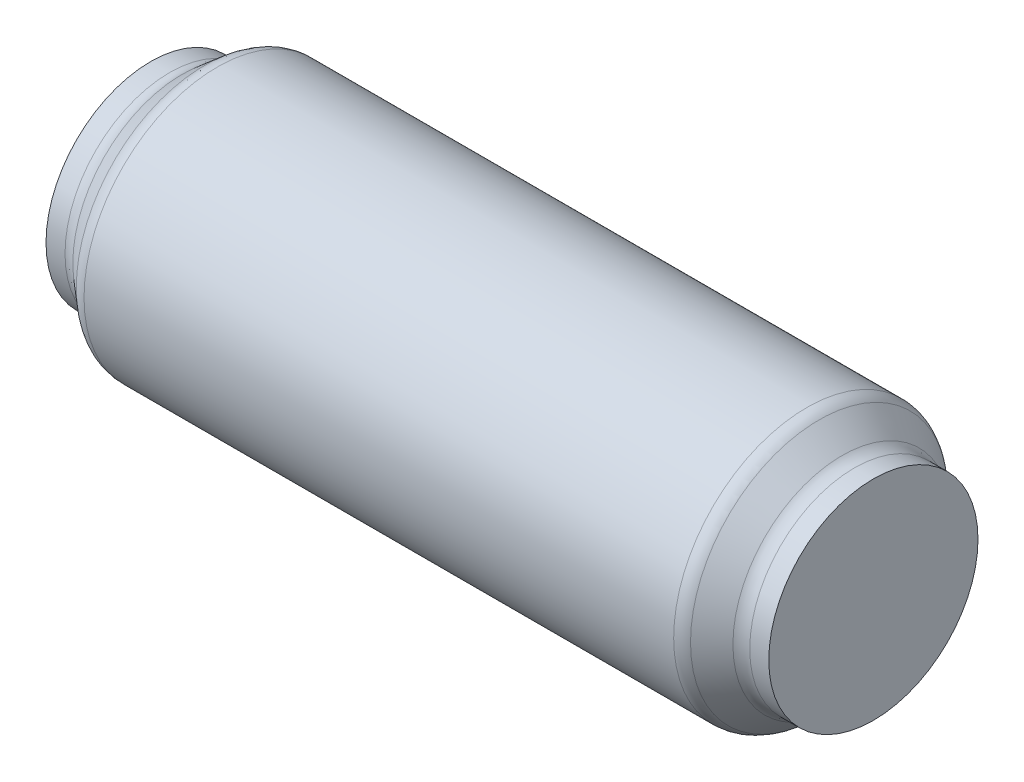
SolidWorks part; units mm, degrees
ref_plane "Front Plane" through (0, 0, 0) normal (0, 0, 1) x (1, 0, 0)
ref_plane "Top Plane" through (0, 0, 0) normal (0, 1, 0) x (1, 0, 0)
ref_plane "Right Plane" through (0, 0, 0) normal (1, 0, 0) x (0, 0, -1)
sketch "Sketch1" plane through (0, 0, 0) normal (0, 1, 0) x (1, 0, 0)
  line L0 (0, 0) -> (95, 0) construction
  line L1 (95, 0) -> (95, 27.5)
  line L2 (95, 27.5) -> (90, 27.5)
  line L3 (86.762, 28.6901) -> (80.738, 33.8099)
  line L4 (77.5, 35) -> (-77.5, 35)
  line L5 (0, 0) -> (0, 35) construction
  line L6 (-86.762, 28.6901) -> (-80.738, 33.8099)
  line L7 (-95, 27.5) -> (-90, 27.5)
  line L8 (-95, 0) -> (-95, 27.5)
  line L10 (-95, 0) -> (95, 0)
  arc A0 (90, 27.5) -> (86.762, 28.6901) centre (90, 32.5) cw
  arc A1 (80.738, 33.8099) -> (77.5, 35) centre (77.5, 30) ccw
  arc A2 (-80.738, 33.8099) -> (-77.5, 35) centre (-77.5, 30) cw
  arc A3 (-90, 27.5) -> (-86.762, 28.6901) centre (-90, 32.5) ccw
  point P10 (0, 35)
  dimension "D1" = 190
  dimension "D5" = 5
  dimension "D6" = 5
  dimension "D2" = 70
  dimension "D3" = 7.5
  dimension "D4" = 5
  dimension "D7" = 17.5
revolve "Revolve1" add sketch "Sketch1" angle 360 about L10
ref_axis "Axis1" through (77.5, 0, 0) along (-1, 0, 0)
